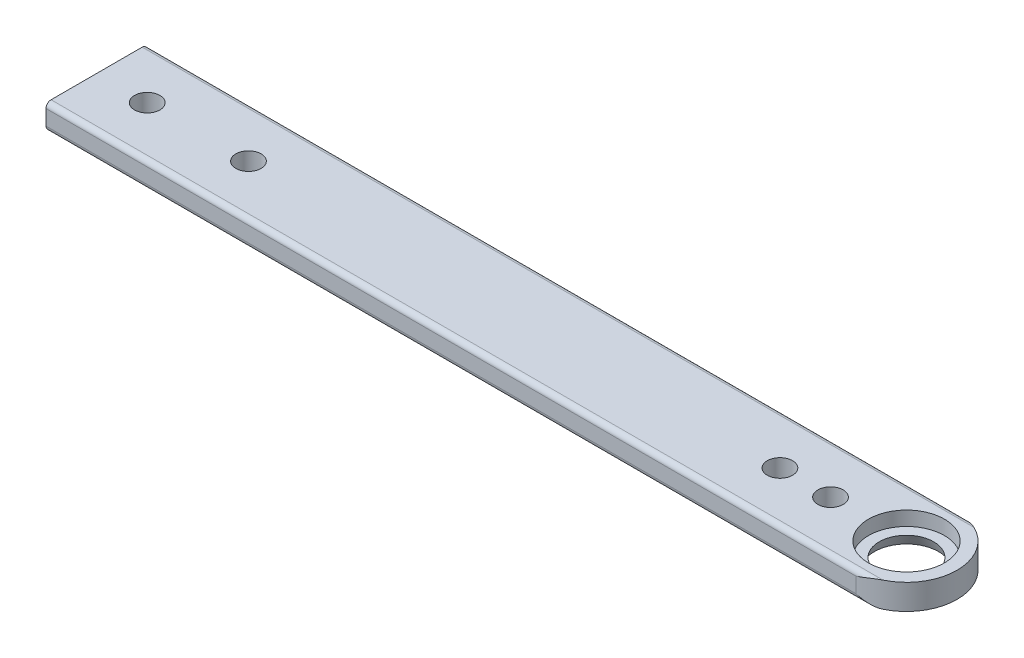
SolidWorks part; units mm, degrees
material "Plain Carbon Steel"
ref_plane "Front Plane" through (0, 0, 0) normal (0, 0, 1) x (1, 0, 0)
ref_plane "Top Plane" through (0, 0, 0) normal (0, 1, 0) x (1, 0, 0)
ref_plane "Right Plane" through (0, 0, 0) normal (1, 0, 0) x (0, 0, -1)
sketch "Sketch1" plane through (0, 0, 0) normal (0, 1, 0) x (1, 0, 0)
  line L1 (107.95, -12.7) -> (-107.95, -12.7)
  line L2 (107.95, -12.7) -> (107.95, 12.7)
  line L3 (107.95, 12.7) -> (-107.95, 12.7)
  line L4 (-107.95, -12.7) -> (-107.95, 12.7)
  line L5 (107.95, -12.7) -> (-107.95, 12.7) construction
  line L6 (107.95, 12.7) -> (-107.95, -12.7) construction
  point P0 (0, 0)
  dimension "D1" = 25.4
  dimension "D2" = 215.9
extrude "Boss-Extrude1" add sketch "Sketch1" along normal blind 6.35
fillet "Fillet1" radius 1.27 4 edges at (0, 0, -12.7) (0, 6.35, -12.7) (0, 0, 12.7) (0, 6.35, 12.7)
sketch "Sketch2" plane through (0, 6.35, 0) normal (0, 1, 0) x (1, 0, 0)
  line L0 (-107.95, 0) -> (107.95, 0) construction
  line L1 (-107.95, 11.43) -> (-107.95, -11.43) construction
  line L2 (107.95, -11.43) -> (107.95, 11.43) construction
  circle A0 centre (-95.25, 0) radius 3.175
  circle A3 centre (95.25, 0) radius 6.35
  circle A7 centre (-69.85, 0) radius 3.175
  dimension "D1" = 12.7
  dimension "D4" = 6.35
  dimension "D2" = 190.5
  dimension "D3" = 12.7
  dimension "D5" = 2
extrude "Cut-Extrude1" cut sketch "Sketch2" against normal through all
sketch "Sketch3" plane through (0, 6.35, 0) normal (0, 1, 0) x (1, 0, 0)
  circle A0 centre (95.25, 0) radius 9.525
  dimension "D1" = 19.05
extrude "Cut-Extrude2" cut sketch "Sketch3" against normal blind 3.5719
sketch "Sketch4" plane through (0, 6.35, 0) normal (0, 1, 0) x (1, 0, 0)
  line L0 (-107.95, 0) -> (107.95, 0) construction
  circle A0 centre (76.2, 0) radius 3.175
  circle A2 centre (63.5, 0) radius 3.175
  dimension "D3" = 6.35
  dimension "D1" = 19.05
  dimension "D2" = 12.7
extrude "Cut-Extrude3" cut sketch "Sketch4" against normal through all
sketch "Sketch5" plane through (0, 6.35, 0) normal (0, 1, 0) x (1, 0, 0)
  line L0 (-107.95, 12.7) -> (107.95, 12.7) construction
  line L1 (107.95, -11.43) -> (107.95, 11.43) construction
  line L2 (107.95, -12.7) -> (-107.95, -12.7) construction
  line L4 (82.55, -12.7) -> (107.95, -12.7)
  line L5 (82.55, -12.7) -> (82.55, 12.7)
  line L6 (82.55, 12.7) -> (107.95, 12.7)
  line L7 (107.95, -12.7) -> (107.95, 12.7)
  line L8 (82.55, -12.7) -> (107.95, 12.7) construction
  line L9 (82.55, 12.7) -> (107.95, -12.7) construction
  circle A0 centre (95.25, 0) radius 12.7
  line M11 (107.95, -11.43) -> (107.95, 11.43)
  line M12 (107.95, 11.43) -> (-107.95, 11.43)
  line M14 (-107.95, -11.43) -> (107.95, -11.43)
extrude "Cut-Extrude4" cut sketch "Sketch5" against normal through all contours A0 L7 M12 | A0 L7 L6 M12 | A0 M14 M11 | A0 L4 L7 M14 region at (103.3706, 6.35, 12.1169) region at (105.9682, 6.35, 8.7575) region at (105.9682, 6.35, -8.7575) region at (103.3706, 6.35, -12.1169)
ref_axis "Axis1" through (95.25, 0, 0) along (0, 1, 0)
ref_plane "Plane1" through (95.25, 0, 0) normal (-1, 0, 0) x (0, 0, 1)
sketch "Sketch6" plane through (95.25, 0, 0) normal (-1, 0, 0) x (0, 0, 1)
  line L0 (0, 0) -> (0, 6.35)
  line L1 (11.43, 6.35) -> (-11.43, 6.35) construction
  line L2 (0, 6.35) -> (-3.6942, -1.9474)
  line L3 (-3.6942, -1.9474) -> (-8.0682, 0)
  line L4 (-8.0682, 0) -> (-4.374, 8.2974)
  line L5 (-4.374, 8.2974) -> (0, 6.35)
  line L6 (-11.43, 0) -> (11.43, 0) construction
  line L7 (0, 0) -> (-6.35, 0)
  line L8 (-6.35, 0) -> (-6.35, 2.7781)
  line L9 (-6.35, 2.7781) -> (0, 2.7781)
  line L10 (-6.35, 0) -> (-8.0682, 0)
  line L11 (-6.35, 2.7781) -> (-6.8313, 2.7781)
  point P14 (-6.35, 2.7997)
  dimension "D1" = 24
  dimension "D2" = 4.7879
  dimension "D3" = 6.35
  dimension "D4" = 2.7781
revolve "Cut-Revolve2" cut sketch "Sketch6" angle 360 about axis through (95.25, 0, 0) along (0, 1, 0) region at (95.25, 1.1287, -6.9578)
